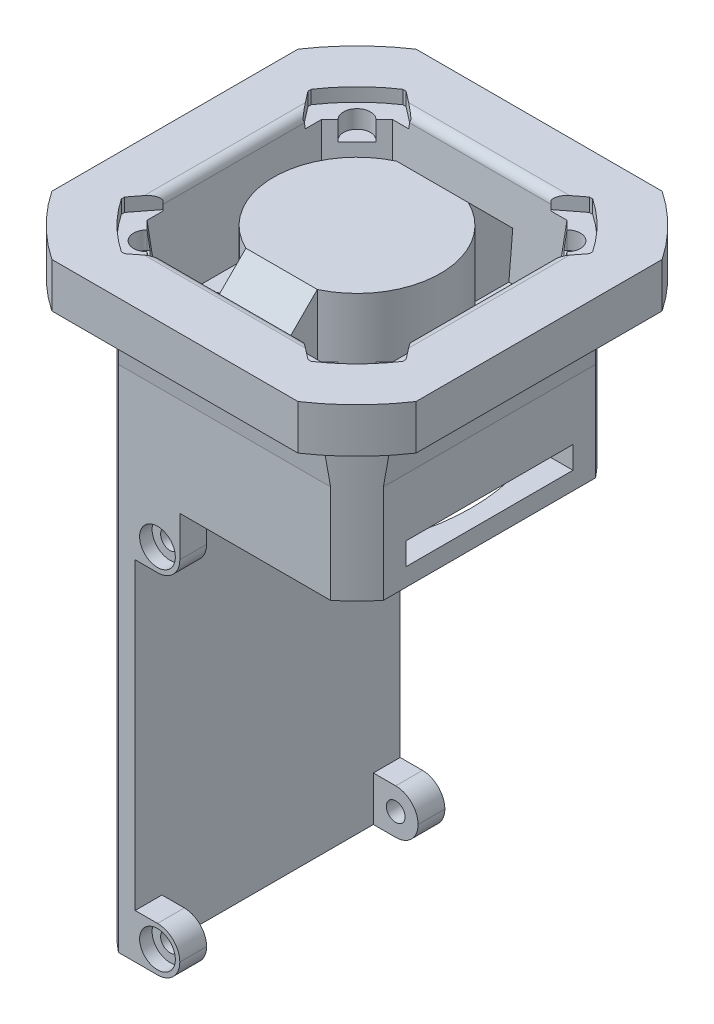
SolidWorks part; units mm, degrees
material "PVC 0.007 Plasticized"
ref_plane "Front Plane" through (0, 0, 0) normal (0, 0, 1) x (1, 0, 0)
ref_plane "Top Plane" through (0, 0, 0) normal (0, 1, 0) x (1, 0, 0)
ref_plane "Right Plane" through (0, 0, 0) normal (1, 0, 0) x (0, 0, -1)
sketch "Sketch1" plane through (0, 0, 0) normal (0, 1, 0) x (1, 0, 0)
  line L1 (0, 0) -> (30, 0)
  line L2 (0, 0) -> (0, 30)
  line L3 (0, 30) -> (30, 30)
  line L4 (30, 0) -> (30, 30)
  dimension "D1" = 30
  dimension "D2" = 30
extrude "Boss-Extrude1" add sketch "Sketch1" along normal blind 10
chamfer "Chamfer1" distance 2 angle 85 4 edges at (15, 0, 0) (30, 0, -15) (15, 0, -30) (0, 0, -15) first distance on face at (15, 0, -15)
shell "Shell1" thickness 2 removed face at (15, 10, -15) outward yes
fillet "Fillet1" radius 4 4 edges at (1.5626, 5, -28.4374) (1.5626, 5, -1.5626) (28.4374, 5, -1.5626) (28.4374, 5, -28.4374) profile chamfer
sketch "Sketch2" plane through (0, 0, 0) normal (0, 1, 0) x (-1, 0, 0)
  circle A1 centre (-15, -15) radius 19
  dimension "D1" = 38
extrude "Cut-Extrude2" cut sketch "Sketch2" along normal through all both and the other way through all flip side to cut
sketch "Sketch6" plane through (0, 0, 0) normal (0, 1, 0) x (1, 0, 0)
  line L0 (28, 24.0152) -> (28, 5.9848) construction
  line L1 (5.9848, 28) -> (24.0152, 28) construction
  circle A0 centre (15, 15) radius 8.1375
  point P4 (28, 15)
  point P7 (15, 28)
  dimension "D1" = 16.275
extrude "Cut-Extrude5" cut sketch "Sketch6" against normal blind 4
sketch "Sketch7" plane through (0, 0, 0) normal (0, 1, 0) x (1, 0, 0)
  line L0 (15, 28) -> (15, 2) construction
  line L1 (2, 5.9848) -> (2, 24.0152) construction
  line L6 (5.9848, 28) -> (24.0152, 28) construction
  line L7 (24.0152, 2) -> (5.9848, 2) construction
  line L8 (3.795, 4.1898) -> (3.795, 25.8102) construction
  line L9 (2, 5.9848) -> (5.9848, 2) construction
  line L10 (5.9848, 28) -> (2, 24.0152) construction
  line L11 (3.795, 15) -> (15, 15) construction
  circle A10 centre (3.795, 15) radius 1.59
  circle A11 centre (4.6394, 20.6315) radius 1.59
  circle A12 centre (8, 25.2285) radius 1.59
  circle A13 centre (4.6394, 9.3685) radius 1.59
  circle A14 centre (8, 4.7715) radius 1.59
  circle A15 centre (22, 4.7715) radius 1.59
  circle A16 centre (25.3606, 9.3685) radius 1.59
  circle A17 centre (26.205, 15) radius 1.59
  circle A18 centre (25.3606, 20.6315) radius 1.59
  circle A19 centre (22, 25.2285) radius 1.59
  arc A20 (3.795, 15) -> (15, 28) centre (15.6631, 16.0995) cw construction
  point P20 (15, 15)
  point P26 (15.6631, 16.0995)
  dimension "D1" = 7
  dimension "D2" = 1.795
  dimension "D3" = 3.18
  dimension "D4" = 3
  dimension "D5" = 5.75
extrude "Cut-Extrude7" cut sketch "Sketch7" against normal blind 0.71 contours A12 | A11 | A10 | A13 | A14 | A15 | A16 | A17 | A18 | A19
sketch "Sketch8" plane through (0, -0.71, 0) normal (0, 1, 0) x (1, 0, 0)
  circle A10 centre (8, 25.2285) radius 0.75
  circle A11 centre (4.6394, 20.6315) radius 0.75
  circle A12 centre (3.795, 15) radius 0.75
  circle A13 centre (4.6394, 9.3685) radius 0.75
  circle A14 centre (8, 4.7715) radius 0.75
  circle A15 centre (22, 25.2285) radius 0.75
  circle A16 centre (25.3606, 20.6315) radius 0.75
  circle A17 centre (26.205, 15) radius 0.75
  circle A18 centre (25.3606, 9.3685) radius 0.75
  circle A19 centre (22, 4.7715) radius 0.75
  dimension "D1" = 1.5
extrude "Cut-Extrude8" cut sketch "Sketch8" against normal through all
sketch "Sketch9" plane through (0, 10, 0) normal (0, 1, 0) x (1, 0, 0)
  line L0 (-0.8825, 25.4281) -> (1.1251, 22.8291)
  line L2 (1.1251, 22.8291) -> (7.1709, 28.8749)
  line L3 (1.1251, 24.8901) -> (5.1099, 28.8749) construction
  line L4 (1.1251, 24.8901) -> (1.1251, 5.1099) construction
  line L5 (24.8901, 28.8749) -> (5.1099, 28.8749) construction
  line L6 (7.1709, 28.8749) -> (4.5719, 30.8825)
  arc A2 (-0.8825, 25.4281) -> (4.5719, 30.8825) centre (15, 15) cw
  line M6 (1.1251, 5.1099) -> (1.1251, 24.8901)
  line M7 (1.1251, 24.8901) -> (5.1099, 28.8749)
  line M8 (5.1099, 28.8749) -> (24.8901, 28.8749)
  dimension "D1" = 8.55
  dimension "D2" = 0
extrude "Cut-Extrude10" cut sketch "Sketch9" against normal blind 1.5 contours L2 M6 M8 M7 | M6 M7 M8 region at (2.5018, 10, -27.4982) region at (3.668, 10, -26.332)
ref_plane "Plane1" through (15, 0, 0) normal (1, 0, 0) x (0, 0, -1)
ref_plane "Plane6" through (0, 0, -29.8327) normal (0, 0, 1) x (1, 0, 0)
mirror "Mirror1" about plane through (15, 0, 0) normal (1, 0, 0) of "Cut-Extrude10"
ref_plane "Plane2" through (0, 0, -15) normal (0, 0, 1) x (1, 0, 0)
mirror "Mirror2" about plane through (0, 0, -15) normal (0, 0, 1) of "Mirror1", "Cut-Extrude10"
sketch "Sketch10" plane through (0, 0, 0) normal (1, 0, 0) x (0, 0, -1)
  line L1 (0.5, -59) -> (29.5, -59)
  line L2 (0.5, -59) -> (0.5, -2)
  line L3 (0.5, -2) -> (29.5, -2)
  line L4 (29.5, -59) -> (29.5, -2)
  line L5 (26.874, -2) -> (3.126, -2) construction
  point P6 (15, -2)
  point P8 (15, -59)
  dimension "D1" = 29
  dimension "D2" = 57
extrude "Boss-Extrude2" add sketch "Sketch10" along normal blind 5
ref_plane "Plane3" through (0, 0, -15) normal (0, 0, 1) x (1, 0, 0)
sketch "Sketch15" plane through (0, 0, -29.8327) normal (0, 0, -1) x (-1, 0, 0)
  line L0 (-29.8327, -2) -> (-29.8327, -13)
  line L1 (-29.8327, -13) -> (-5, -13)
  line L2 (-5, -59) -> (-5, -2) construction
  line L3 (-5, -13) -> (-5, -10)
  line L4 (-5, -10) -> (-26.8327, -10)
  line L5 (-26.8327, -10) -> (-26.8327, -2)
  line L7 (-26.8327, -2) -> (-29.8327, -2)
  dimension "D1" = 11
  dimension "D2" = 3
  dimension "D3" = 3
extrude "Boss-Extrude4" add sketch "Sketch15" against normal up to vertex (29.6653 mm away) up to point (26.874, -2, -0.1673)
ref_plane "MIDPLANE" through (0, 0, -15) normal (0, 0, -1) x (-1, 0, 0)
sketch "Sketch16" plane through (0, -13, 0) normal (0, -1, 0) x (1, 0, 0)
  line L2 (2.205, -15) -> (27.795, -15) construction
  line L8 (26.8327, -3.1673) -> (8, -3.1673)
  line L9 (8, -3.1673) -> (8, -26.8327)
  line L10 (8, -26.8327) -> (26.8327, -26.8327)
  line L11 (26.8327, -26.8327) -> (26.8327, -3.1673)
  line L12 (24.144, -3.1673) -> (5.856, -3.1673)
  line L14 (5.856, -26.8327) -> (24.144, -26.8327)
  arc A1 (5.856, -3.1673) -> (5.856, -26.8327) centre (23.205, -15) ccw
  circle A2 centre (3.795, -15) radius 1.59 construction
  arc A3 (24.144, -3.1673) -> (24.144, -26.8327) centre (6.795, -15) cw
  circle A5 centre (26.205, -15) radius 1.59 construction
  dimension "D2" = 21
  dimension "D1" = 3
extrude "Cut-Extrude14" cut sketch "Sketch16" against normal up to surface (11 mm away) up to face at (10.6018, -2, -15)
sketch "Sketch17" plane through (29.8327, 0, 0) normal (1, 0, 0) x (0, 0, -1)
  line L12 (3.1673, -5) -> (3.1673, -10)
  line L13 (3.1673, -10) -> (26.8327, -10)
  line L14 (26.8327, -10) -> (26.8327, -5)
  line L15 (26.8327, -5) -> (3.1673, -5)
  line L16 (3.1673, -5) -> (3.1673, -10)
  line L17 (3.1673, -10) -> (26.8327, -10)
  line L18 (26.8327, -10) -> (26.8327, -5)
  line L19 (26.8327, -5) -> (3.1673, -5)
  dimension "D1" = 3
extrude "Cut-Extrude15" cut sketch "Sketch17" against normal blind 10
fillet "Fillet3" [suppressed] radius 3
sketch "Sketch18" [suppressed] plane through (0, 0, 0) normal (-1, 0, 0) x (0, 0, 1)
  line L4 (-0.5, -59) -> (-29.5, -59) construction
  line L12 (-6.5, -21) -> (-23.5, -21)
  line L13 (-23.5, -21) -> (-23.5, -53)
  line L14 (-23.5, -53) -> (-6.5, -53)
  line L15 (-6.5, -53) -> (-6.5, -21)
  dimension "D1" = 6
  dimension "D2" = 32
  dimension "D3" = 17
extrude "Cut-Extrude16" [suppressed] cut sketch "Sketch18" against normal through all
sketch "Sketch19" plane through (0, 8.5, 0) normal (0, 1, 0) x (1, 0, 0)
  line L2 (1.2563, 24.7589) -> (5.2411, 28.7437) construction
  line L3 (2.1881, 25.6906) -> (3.0811, 24.7975)
  line L4 (3.0811, 24.7975) -> (5.1997, 26.9161)
  line L5 (5.1997, 26.9161) -> (4.3094, 27.8119)
  arc A1 (2.1881, 25.6906) -> (4.3094, 27.8119) centre (3.2487, 26.7513) cw
  dimension "D3" = 1.5
  dimension "D2" = 3
extrude "Cut-Extrude18" cut sketch "Sketch19" against normal blind 2
mirror "Mirror4" about plane through (15, 0, 0) normal (1, 0, 0) of "Cut-Extrude18" second plane through (0, 0, -15) second plane normal (0, 0, 1)
fillet "Fillet6" radius 1 4 edges at (1.1251, 10, -15) (15, 10, -1.1251) (28.8749, 10, -15) (15, 10, -28.8749)
ref_plane "Plane4" through (0, 0, -15) normal (0, 0, -1) x (-1, 0, 0)
sketch "Sketch20" [suppressed] plane through (0, 0, -15) normal (0, 0, -1) x (-1, 0, 0)
  line L0 (0, -2) -> (0, -56) construction
  line L1 (0, -6) -> (0, -15.5)
  line L2 (0, -6) -> (9.5, -6)
  line L3 (0, -2) -> (-2.7048, -2) construction
  arc A0 (0, -15.5) -> (9.5, -6) centre (0, -6) ccw
  dimension "D1" = 4
  dimension "D2" = 9.5
extrude "Boss-Extrude5" [suppressed] add sketch "Sketch20" along normal mid plane 20
sketch "Sketch21" plane through (0, 0, 0) normal (0, 1, 0) x (1, 0, 0)
  circle A0 centre (15, 15) radius 9.3375
  circle A1 centre (15, 15) radius 8.1375
  circle A2 centre (15, 15) radius 8.1375 construction
  dimension "D1" = 18.675
extrude "Boss-Extrude6" add sketch "Sketch21" along normal blind 7
sketch "Sketch22" plane through (0, 7, 0) normal (0, 1, 0) x (1, 0, 0)
  circle A0 centre (15, 15) radius 9.3375
  circle A1 centre (15, 15) radius 9.3375 construction
  circle A2 centre (15, 15) radius 9.3375 construction
extrude "Boss-Extrude7" add sketch "Sketch22" along normal blind 1
ref_plane "Plane5" through (35.383, 0, 0) normal (1, 0, 0) x (0, 0, -1)
sketch "Sketch23" plane through (35.383, 0, 0) normal (1, 0, 0) x (0, 0, -1)
  line L1 (22, 10) -> (8, 10)
  line L2 (22, 10) -> (22, 5)
  line L3 (22, 5) -> (8, 5)
  line L4 (8, 10) -> (8, 5)
  line L5 (25.4281, 10) -> (4.5719, 10) construction
  point P7 (15, 10)
  point P8 (15, 10)
  dimension "D1" = 5
  dimension "D2" = 14
extrude "Boss-Extrude8" add sketch "Sketch23" against normal up to next
pattern_circular "CirPattern1" count 4 over 360 about axis through (15, 8, -15) along (0, 1, 0) skipping 2 of "Boss-Extrude8"
sketch "Sketch24" plane through (0, -2, 0) normal (0, 1, 0) x (1, 0, 0)
  line L2 (29.8327, 26.874) -> (29.8327, 29.8327)
  line L3 (29.8327, 26.874) -> (29.8327, 29.8327)
  line L4 (2.722, 29.5) -> (0, 29.5)
  line L5 (0, 29.5) -> (0, 0.5)
  line L6 (0, 0.5) -> (2.722, 0.5)
  line L7 (0.1673, 3.126) -> (0.1673, 26.874)
  line L8 (2.722, 29.5) -> (0, 29.5)
  line L9 (0, 29.5) -> (0, 0.5)
  line L10 (0, 0.5) -> (2.722, 0.5)
  line L11 (0.1673, 3.126) -> (0.1673, 26.874)
  line L14 (29.8327, 26.874) -> (29.8327, 29.8327)
  line L15 (29.8327, 26.874) -> (29.8327, 29.8327)
  line L18 (29.8327, 29.8327) -> (26.874, 29.8327)
  line L19 (29.8327, 29.8327) -> (26.874, 29.8327)
  line L20 (26.874, 0.1673) -> (29.8327, 0.1673)
  line L21 (29.8327, 0.1673) -> (29.8327, 3.126)
  line L23 (29.8327, 0.1673) -> (29.8327, 3.126)
  line L24 (29.8327, 29.8327) -> (26.874, 29.8327)
  line L25 (29.8327, 29.8327) -> (26.874, 29.8327)
  line L27 (26.874, 0.1673) -> (29.8327, 0.1673)
  arc A1 (29.8327, 26.874) -> (26.874, 29.8327) centre (15, 15) ccw
  arc A2 (2.722, 29.5) -> (0.1673, 26.874) centre (15, 15) ccw
  arc A3 (0.1673, 3.126) -> (2.722, 0.5) centre (15, 15) ccw
  arc A4 (2.722, 29.5) -> (0.1673, 26.874) centre (15, 15) ccw
  arc A5 (0.1673, 3.126) -> (2.722, 0.5) centre (15, 15) ccw
  arc A7 (29.8327, 26.874) -> (26.874, 29.8327) centre (15, 15) ccw
  arc A9 (29.8327, 26.874) -> (26.874, 29.8327) centre (15, 15) ccw
  arc A10 (26.874, 0.1673) -> (29.8327, 3.126) centre (15, 15) ccw
  arc A11 (26.874, 0.1673) -> (29.8327, 3.126) centre (15, 15) ccw
  arc A12 (29.8327, 26.874) -> (26.874, 29.8327) centre (15, 15) ccw
  arc M7 (0.1673, 26.874) -> (2.722, 29.5) centre (15, 15) cw
  line M8 (2.722, 29.5) -> (0, 29.5)
  line M9 (0, 29.5) -> (0, 0.5)
  line M10 (0, 0.5) -> (2.722, 0.5)
  arc M11 (2.722, 0.5) -> (0.1673, 3.126) centre (15, 15) cw
  line M12 (0.1673, 3.126) -> (0.1673, 26.874)
  dimension "D1" = 0
  dimension "D2" = 0
  dimension "D3" = 0
  dimension "D4" = 0
extrude "Cut-Extrude19" cut sketch "Sketch24" against normal up to surface (57 mm away) contours A11 L27 L23 | A12 L3 L25 | M12 M7 M8 M9 M10 M11 region at (28.8831, -2, -28.8831) region at (1.1724, -2, -28.4518) region at (28.8831, -2, -1.1169) up to face at (2.5, -59, -15)
sketch "Sketch25" plane through (0, -2, 0) normal (0, -1, 0) x (1, 0, 0)
  line L0 (5, -29.5) -> (2.722, -29.5) construction
  line L1 (3.126, -29.8327) -> (26.8327, -29.8327) construction
  line L2 (5, -29.5) -> (5, -29.8327) construction
  line L3 (5, -0.5) -> (2.722, -0.5) construction
  line L4 (5, -0.1673) -> (5, -0.5) construction
  line L5 (26.8327, -0.1673) -> (3.126, -0.1673) construction
  line L6 (5, -29.5) -> (2.722, -29.5)
  line L7 (3.126, -29.8327) -> (5, -29.8327)
  line L8 (5, -29.5) -> (5, -29.8327)
  line L9 (5, -0.5) -> (2.722, -0.5)
  line L10 (5, -0.1673) -> (5, -0.5)
  line L11 (26.8327, -0.1673) -> (3.126, -0.1673)
  line L12 (26.8327, -0.1673) -> (3.126, -0.1673) construction
  line L13 (5, -0.1673) -> (3.126, -0.1673)
  arc A0 (2.722, -29.5) -> (3.126, -29.8327) centre (15, -15) ccw construction
  arc A2 (2.722, -29.5) -> (3.126, -29.8327) centre (15, -15) ccw
  arc A4 (3.126, -0.1673) -> (2.722, -0.5) centre (15, -15) ccw construction
  arc A5 (3.126, -0.1673) -> (2.722, -0.5) centre (15, -15) ccw
  arc M3 (3.126, -0.1673) -> (2.722, -0.5) centre (15, -15) ccw
  line M4 (2.722, -0.5) -> (5, -0.5)
  line M32 (26.8327, -0.1673) -> (3.126, -0.1673)
extrude "Boss-Extrude9" add sketch "Sketch25" along normal up to surface (57 mm away) contours L10 M32 M3 M4 | L6 A2 L7 L8 region at (3.9578, -2, -0.3391) up to face at (2.6086, -59, -15)
sketch "Sketch51" plane through (0, -10, 0) normal (0, 1, 0) x (1, 0, 0)
  line L4 (26.8327, 26.8327) -> (26.8327, 29.8327)
  line L5 (26.8327, 3.1673) -> (29.8327, 3.1673)
  line L6 (29.8327, 3.1673) -> (29.8327, 26.8327)
  line L7 (29.8327, 26.8327) -> (26.8327, 26.8327)
  line L8 (26.8327, 26.8327) -> (26.8327, 29.8327)
  line L9 (26.8327, 3.1673) -> (29.8327, 3.1673)
  line L10 (29.8327, 3.1673) -> (29.8327, 26.8327)
  line L11 (29.8327, 26.8327) -> (26.8327, 26.8327)
  line L12 (24.144, 3.1673) -> (5.856, 3.1673)
  line L13 (5, 4.5321) -> (5, 0.1673)
  line L14 (5, 0.1673) -> (26.8327, 0.1673)
  line L15 (26.8327, 0.1673) -> (26.8327, 3.1673)
  line L16 (26.8327, 26.8327) -> (26.8327, 29.8327)
  line L17 (26.8327, 26.8327) -> (26.8327, 29.8327)
  line L18 (26.8327, 29.8327) -> (5, 29.8327)
  line L19 (26.8327, 29.8327) -> (5, 29.8327)
  line L20 (24.144, 3.1673) -> (5.856, 3.1673)
  line L21 (5, 4.5321) -> (5, 0.1673)
  line L22 (5, 0.1673) -> (26.8327, 0.1673)
  line L23 (26.8327, 0.1673) -> (26.8327, 3.1673)
  line L36 (5, 29.8327) -> (5, 25.4679)
  line L37 (5, 29.8327) -> (5, 25.4679)
  line L38 (5.856, 26.8327) -> (24.144, 26.8327)
  line L39 (5.856, 26.8327) -> (24.144, 26.8327)
  line L47 (26.8327, 0.1673) -> (26.8327, 3.1673)
  line L49 (26.8327, 3.1673) -> (29.8327, 3.1673)
  line L50 (26.8327, 3.1673) -> (29.8327, 3.1673)
  line L51 (29.8327, 3.1673) -> (29.8327, 26.8327)
  line L52 (29.8327, 3.1673) -> (29.8327, 26.8327)
  line L53 (29.8327, 26.8327) -> (26.8327, 26.8327)
  line L54 (29.8327, 26.8327) -> (26.8327, 26.8327)
  line L55 (24.144, 3.1673) -> (5.856, 3.1673)
  line L56 (24.144, 3.1673) -> (5.856, 3.1673)
  line L57 (5, 4.5321) -> (5, 0.1673)
  line L58 (5, 4.5321) -> (5, 0.1673)
  line L59 (5, 0.1673) -> (26.8327, 0.1673)
  line L60 (5, 0.1673) -> (26.8327, 0.1673)
  line L61 (26.8327, 0.1673) -> (26.8327, 3.1673)
  line L62 (26.8327, 0.1673) -> (26.8327, 3.1673)
  line L63 (26.8327, 29.8327) -> (5, 29.8327)
  line L64 (26.8327, 29.8327) -> (5, 29.8327)
  line L65 (5, 29.8327) -> (5, 25.4679)
  line L66 (5, 29.8327) -> (5, 25.4679)
  line L67 (5.856, 26.8327) -> (24.144, 26.8327)
  line L68 (5.856, 26.8327) -> (24.144, 26.8327)
  line L69 (24.144, 3.1673) -> (5.856, 3.1673)
  line L70 (24.144, 3.1673) -> (5.856, 3.1673)
  line L71 (5, 4.5321) -> (5, 0.1673)
  line L72 (5, 4.5321) -> (5, 0.1673)
  line L73 (5, 0.1673) -> (26.8327, 0.1673)
  line L74 (5, 0.1673) -> (26.8327, 0.1673)
  line L75 (26.8327, 3.1673) -> (29.8327, 3.1673)
  line L76 (26.8327, 3.1673) -> (29.8327, 3.1673)
  line L77 (29.8327, 3.1673) -> (29.8327, 26.8327)
  line L78 (29.8327, 3.1673) -> (29.8327, 26.8327)
  line L79 (29.8327, 26.8327) -> (26.8327, 26.8327)
  line L80 (29.8327, 26.8327) -> (26.8327, 26.8327)
  line L81 (26.8327, 26.8327) -> (26.8327, 29.8327)
  line L82 (26.8327, 26.8327) -> (26.8327, 29.8327)
  line L83 (26.8327, 29.8327) -> (5, 29.8327)
  line L84 (26.8327, 29.8327) -> (5, 29.8327)
  line L85 (5, 29.8327) -> (5, 25.4679)
  line L86 (5, 29.8327) -> (5, 25.4679)
  line L87 (5.856, 26.8327) -> (24.144, 26.8327)
  line L88 (5.856, 26.8327) -> (24.144, 26.8327)
  arc A1 (5.856, 26.8327) -> (5, 25.4679) centre (23.205, 15) ccw
  arc A3 (5.856, 26.8327) -> (5, 25.4679) centre (23.205, 15) ccw
  arc A5 (5, 4.5321) -> (5.856, 3.1673) centre (23.205, 15) ccw
  arc A6 (5, 4.5321) -> (5.856, 3.1673) centre (23.205, 15) ccw
  arc A9 (24.144, 3.1673) -> (24.144, 26.8327) centre (6.795, 15) ccw
  arc A10 (24.144, 3.1673) -> (24.144, 26.8327) centre (6.795, 15) ccw
  arc A11 (5, 4.5321) -> (5.856, 3.1673) centre (23.205, 15) ccw
  arc A12 (5, 4.5321) -> (5.856, 3.1673) centre (23.205, 15) ccw
  arc A13 (5.856, 26.8327) -> (5, 25.4679) centre (23.205, 15) ccw
  arc A14 (5.856, 26.8327) -> (5, 25.4679) centre (23.205, 15) ccw
  arc A15 (24.144, 3.1673) -> (24.144, 26.8327) centre (6.795, 15) ccw
  arc A16 (24.144, 3.1673) -> (24.144, 26.8327) centre (6.795, 15) ccw
  arc A17 (5, 4.5321) -> (5.856, 3.1673) centre (23.205, 15) ccw
  arc A18 (5, 4.5321) -> (5.856, 3.1673) centre (23.205, 15) ccw
  arc A19 (5.856, 26.8327) -> (5, 25.4679) centre (23.205, 15) ccw
  arc A20 (5.856, 26.8327) -> (5, 25.4679) centre (23.205, 15) ccw
  arc A21 (24.144, 3.1673) -> (24.144, 26.8327) centre (6.795, 15) ccw
  arc A22 (24.144, 3.1673) -> (24.144, 26.8327) centre (6.795, 15) ccw
  line M18 (26.8327, 29.8327) -> (5, 29.8327)
  line M19 (5, 29.8327) -> (5, 25.4679)
  line M20 (5.856, 26.8327) -> (24.144, 26.8327)
  dimension "D1" = 0
  dimension "D2" = 0
  dimension "D3" = 0
extrude "Boss-Extrude35" add sketch "Sketch51" along normal up to surface (8 mm away) contours L10 L11 L8 L9 | L22 L23 L20 L21 | M19 M20 M18 region at (28.3327, -10, -26.4458)
sketch "Sketch52" plane through (0, -13, 0) normal (0, -1, 0) x (1, 0, 0)
  line L0 (5.856, -3.1673) -> (5, -3.1673)
  line L1 (5, -0.1673) -> (5, -4.5321) construction
  line L2 (5, -3.1673) -> (5, -4.5321)
  line L3 (5.856, -26.8327) -> (5, -26.8327)
  line L4 (5, -25.4679) -> (5, -29.8327) construction
  line L5 (5, -26.8327) -> (5, -25.4679)
  arc A1 (5, -25.4679) -> (5.856, -26.8327) centre (23.205, -15) ccw construction
  arc A2 (5, -25.4679) -> (5.856, -26.8327) centre (23.205, -15) ccw
  arc A3 (5.856, -3.1673) -> (5, -4.5321) centre (23.205, -15) ccw construction
  arc A4 (5.856, -3.1673) -> (5, -4.5321) centre (23.205, -15) ccw
extrude "Cut-Extrude28" cut sketch "Sketch52" against normal up to surface (11 mm away)
sketch "Sketch26" plane through (0, 0, -29.8327) normal (0, 0, -1) x (-1, 0, 0)
  line L0 (-5, -59) -> (-5, -13) construction
  line L1 (-5, -59) -> (-10, -59)
  line L2 (-5, -59) -> (-5, -54)
  line L3 (-5, -54) -> (-10, -54)
  line L4 (-10, -59) -> (-10, -54)
  line L6 (-5, -13) -> (-5, -20)
  line L7 (-5, -20) -> (-10, -20)
  line L10 (-10, -20) -> (-10, -13)
  line L11 (-26.874, -13) -> (-5, -13) construction
  line L12 (-10, -13) -> (-5, -13)
  circle A0 centre (-7.5, -56.5) radius 2
  circle A1 centre (-7.5, -56.5) radius 1.05
  circle A2 centre (-7.5, -17.5) radius 2
  circle A3 centre (-7.5, -17.5) radius 1.05
  point P9 (-10, -56.5)
  point P10 (-7.5, -54)
  point P19 (-7.5, -20)
  line M17 (-26.874, -13) -> (-5, -13)
  line M18 (-5, -13) -> (-5, -59)
  dimension "D2" = 4
  dimension "D3" = 2.1
  dimension "D5" = 4
  dimension "D6" = 2.1
  dimension "D1" = 5
  dimension "D4" = 5
  dimension "D7" = 2.5
  dimension "D8" = 39
extrude "Boss-Extrude10" add sketch "Sketch26" against normal blind 3 contours L4 L1 L3 A0 M18 | L10 L7 A2 M18 M17 | A0 A1 | A2 A3 | A3 | A1 region at (7.5, -19.914, -29.8327) region at (7.5, -58.9293, -29.8327) region at (9.4434, -56.5, -29.8327) region at (9.4434, -17.5, -29.8327) region at (7.5, -17.5, -29.8327)
extrude "Cut-Extrude20" cut sketch "Sketch26<4>" against normal blind 1.4 contours A0 A1 | A2 A3 region at (9.4434, -56.5, -29.8327) region at (9.4434, -17.5, -29.8327)
sketch "Sketch26<4>" plane through (0, 0, -29.8327) normal (0, 0, -1) x (-1, 0, 0) same geometry as "Sketch26"
extrude "Cut-Extrude21" cut sketch "Sketch26<6>" against normal up to next contours A1 | A3 region at (7.5, -56.5, -29.8327) region at (7.5, -17.5, -29.8327)
sketch "Sketch26<6>" plane through (0, 0, -29.8327) normal (0, 0, -1) x (-1, 0, 0) same geometry as "Sketch26"
mirror "Mirror5" about plane through (0, 0, -15) normal (0, 0, -1) of "Boss-Extrude9", "Boss-Extrude10", "Cut-Extrude20", "Cut-Extrude21"
fillet "Fillet7" radius 2.5 6 edges at (10, -20, -28.3327) (10, -54, -28.3327) (10, -59, -28.3327) (10, -20, -1.6673) (10, -54, -1.6673) (10, -59, -1.6673)
sketch "Sketch28" plane through (0, 0, 5.383) normal (0, 0, 1) x (1, 0, 0)
  line L1 (35.383, 10) -> (35.383, 5) construction
  line L2 (35.383, 10) -> (35.383, 5)
  line L4 (22, 5) -> (22, 10)
  line L5 (22, 10) -> (8, 10)
  line L6 (8, 10) -> (8, 5)
  line L7 (8, 5) -> (22, 5)
  line L9 (35.383, 10) -> (8, 10)
  line L10 (8, 10) -> (8, 5)
  line L11 (8, 5) -> (35.383, 5)
  line M5 (22, 5) -> (22, 10)
  dimension "D1" = 0
extrude "Boss-Extrude19" add sketch "Sketch28" against normal up to surface (4.5005 mm away) contours L11 L2 L9 M5 region at (28.6915, 7.5, 5.383) up to face at (15, 6.6909, 0.593)
sketch "Sketch30" plane through (35.383, 0, 0) normal (1, 0, 0) x (0, 0, -1)
  line L0 (-0.4451, 5) -> (8, 5)
  line L1 (8, 5) -> (8, 10)
  line L2 (8, 10) -> (-0.8825, 10)
  line L3 (-0.8825, 10) -> (-0.4451, 5)
extrude "Boss-Extrude21" add sketch "Sketch30" against normal up to surface (4.5005 mm away) up to face at (30.593, 6.6909, -15)
sketch "Sketch31" plane through (0, 10, 0) normal (0, 1, 0) x (1, 0, 0)
  line L14 (25.6253, -0.7513) -> (25.2582, -0.7513) construction
  line L15 (24.0154, 0.2088) -> (25.4281, -0.8825) construction
  line L16 (25.4281, -0.8825) -> (30.8825, -0.8825) construction
  line L18 (30.8825, -0.8825) -> (30.8825, 4.5719) construction
  line L19 (25.6253, -0.7513) -> (25.2582, -0.7513)
  line L20 (25.2582, -0.7513) -> (25.4281, -0.8825)
  line L21 (25.4281, -0.8825) -> (30.8825, -0.8825)
  line L29 (30.8825, 4.5719) -> (29.7912, 5.9846) construction
  line L30 (30.8825, -0.8825) -> (30.8825, 4.5719)
  line L31 (30.7513, 4.7418) -> (30.7513, 4.3747) construction
  line L32 (30.8825, 4.5719) -> (30.7513, 4.7418)
  line L33 (30.7513, 4.7418) -> (30.7513, 4.3747)
  arc A4 (25.6253, -0.7513) -> (30.7513, 4.3747) centre (15, 15) ccw construction
  arc A7 (25.6253, -0.7513) -> (30.7513, 4.3747) centre (15, 15) ccw
extrude "Boss-Extrude22" add sketch "Sketch31" against normal up to surface (5 mm away) up to face at (25.5209, 5, -4.4791)
mirror "Mirror6" about plane through (0, 0, -15) normal (0, 0, 1) of "Boss-Extrude21"
sketch "Sketch33" plane through (22, 0, 0) normal (1, 0, 0) x (0, 0, -1)
  line L4 (30.8825, 10) -> (30.4451, 5)
  line L5 (30.4451, 5) -> (35.383, 5)
  line L6 (35.383, 5) -> (35.383, 10)
  line L7 (35.383, 10) -> (30.8825, 10)
  line L8 (30.8825, 10) -> (30.4451, 5)
  line L9 (30.4451, 5) -> (35.383, 5)
  line L10 (35.383, 5) -> (35.383, 10)
  line L11 (35.383, 10) -> (30.8825, 10)
  dimension "D1" = 0
extrude "Boss-Extrude23" add sketch "Sketch33" along normal up to surface (13.383 mm away) up to face at (35.383, 7.5, -12.6404)
sketch "Sketch34" plane through (0, 10, 0) normal (0, 1, 0) x (1, 0, 0)
  line L0 (30.7513, 25.6253) -> (30.7513, 25.2582) construction
  line L1 (30.8825, 25.4281) -> (29.7912, 24.0154) construction
  line L2 (30.8825, 30.8825) -> (30.8825, 25.4281) construction
  line L3 (30.8825, 30.8825) -> (25.4281, 30.8825) construction
  line L4 (24.0154, 29.7912) -> (25.4281, 30.8825) construction
  line L5 (25.2582, 30.7513) -> (25.6253, 30.7513) construction
  line L6 (30.7513, 25.6253) -> (30.7513, 25.2582)
  line L7 (30.8825, 25.4281) -> (30.7513, 25.2582)
  line L8 (30.8825, 30.8825) -> (30.8825, 25.4281)
  line L9 (30.8825, 30.8825) -> (25.4281, 30.8825)
  line L10 (25.2582, 30.7513) -> (25.4281, 30.8825)
  line L11 (25.2582, 30.7513) -> (25.6253, 30.7513)
  arc A0 (30.7513, 25.6253) -> (25.6253, 30.7513) centre (15, 15) ccw construction
  arc A1 (30.7513, 25.6253) -> (25.6253, 30.7513) centre (15, 15) ccw
extrude "Boss-Extrude25" add sketch "Sketch34" against normal up to surface (5 mm away) up to face at (22.4011, 5, -16.3878)
sketch "Sketch35" plane through (0, 10, 0) normal (0, 1, 0) x (1, 0, 0)
  line L2 (35.383, 35.383) -> (35.383, -5.383) construction
  line L3 (-0.8825, 15) -> (35.383, 15) construction
  line L4 (-0.8825, 25.4281) -> (-0.8825, 4.5719) construction
  line L10 (35.383, -5.383) -> (8, -5.383) construction
  line L11 (35.383, -5.383) -> (28.7729, -5.383)
  line L12 (35.383, 35.383) -> (35.383, 15)
  line L13 (35.383, 1.2271) -> (35.383, -5.383)
  line L14 (35.383, 35.383) -> (28.7729, 35.383)
  line L15 (35.383, 28.7729) -> (35.383, 35.383)
  arc A4 (28.7729, 35.383) -> (35.383, 28.7729) centre (15, 15) cw
  arc A5 (28.757, -5.3938) -> (35.3938, 1.243) centre (15, 15) ccw
  arc A6 (28.7729, -5.383) -> (35.383, 1.2271) centre (15, 15) ccw
  arc A8 (25.6253, -0.7513) -> (30.7513, 4.3747) centre (15, 15) ccw construction
  line M20 (8, -5.383) -> (35.383, -5.383)
  line M21 (35.383, -5.383) -> (35.383, 35.383)
  line M22 (35.383, 35.383) -> (8, 35.383)
  dimension "D1" = 5.6
extrude "Cut-Extrude22" cut sketch "Sketch35" against normal up to surface (5 mm away) contours A6 M20 M21 | A4 L12 M22 region at (33.3228, 10, -33.3228) region at (33.3228, 10, 3.3228) up to face at (21.6147, 5, -15)
sketch "Sketch39" plane through (8, 0, 0) normal (-1, 0, 0) x (0, 0, 1)
  line L4 (-30.4451, 5) -> (-30.8825, 10)
  line L5 (-30.8825, 10) -> (-35.383, 10)
  line L6 (-35.383, 10) -> (-35.383, 5)
  line L7 (-35.383, 5) -> (-30.4451, 5)
  line L8 (-30.4451, 5) -> (-30.8825, 10)
  line L9 (-30.8825, 10) -> (-35.383, 10)
  line L10 (-35.383, 10) -> (-35.383, 5)
  line L11 (-35.383, 5) -> (-30.4451, 5)
  dimension "D1" = 0
mirror "Mirror10" about plane through (15, 0, 0) normal (1, 0, 0) of "Boss-Extrude8", "Boss-Extrude19", "Boss-Extrude23"
sketch "Sketch41" [suppressed] plane through (-5.383, 0, 0) normal (-1, 0, 0) x (0, 0, 1)
  line L0 (-30.4451, 5) -> (-22, 5)
  line L1 (-22, 5) -> (-22, 10)
  line L2 (-22, 10) -> (-30.8825, 10)
  line L3 (-30.8825, 10) -> (-30.4451, 5)
sketch "Sketch44" plane through (0, 0, -22) normal (0, 0, -1) x (-1, 0, 0)
  line L4 (5.383, 10) -> (0.8825, 10)
  line L5 (0.8825, 10) -> (0.4451, 5)
  line L6 (0.4451, 5) -> (5.383, 5)
  line L7 (5.383, 5) -> (5.383, 10)
  line L8 (5.383, 10) -> (0.8825, 10)
  line L9 (0.8825, 10) -> (0.4451, 5)
  line L10 (0.4451, 5) -> (5.383, 5)
  line L11 (5.383, 5) -> (5.383, 10)
  dimension "D1" = 0
extrude "Boss-Extrude32" add sketch "Sketch44" along normal up to surface and the other way up to surface up to face at (1.1426, 7.8363, -30.6932) other way up to face at (1.1426, 7.8363, 0.6932)
sketch "Sketch45" plane through (0, 10, 0) normal (0, 1, 0) x (1, 0, 0)
  line L3 (-0.7513, 25.2582) -> (-0.7513, 25.6253) construction
  line L4 (-0.8825, 25.4281) -> (0.2088, 24.0154) construction
  line L5 (-0.8825, 30.8825) -> (-0.8825, 25.4281) construction
  line L6 (-0.8825, 30.8825) -> (4.5719, 30.8825) construction
  line L7 (5.9846, 29.7912) -> (4.5719, 30.8825) construction
  line L8 (4.3747, 30.7513) -> (4.7418, 30.7513) construction
  line L10 (-0.7513, 25.2582) -> (-0.7513, 25.6253)
  line L11 (-0.8825, 25.4281) -> (-0.7513, 25.2582)
  line L12 (-0.8825, 30.8825) -> (-0.8825, 25.4281)
  line L13 (-0.8825, 30.8825) -> (4.5719, 30.8825)
  line L14 (4.7418, 30.7513) -> (4.5719, 30.8825)
  line L15 (4.3747, 30.7513) -> (4.7418, 30.7513)
  arc A0 (4.3747, 30.7513) -> (-0.7513, 25.6253) centre (15, 15) ccw construction
  arc A1 (4.3747, 30.7513) -> (-0.7513, 25.6253) centre (15, 15) ccw
extrude "Boss-Extrude33" add sketch "Sketch45" against normal up to surface (5 mm away) up to face at (19.6966, 5, -15)
mirror "Mirror11" about plane through (0, 0, -15) normal (0, 0, 1) of "Boss-Extrude33"
sketch "Sketch46" plane through (0, 10, 0) normal (0, 1, 0) x (1, 0, 0)
  line L0 (-5.383, 35.383) -> (28.7729, 35.383) construction
  line L1 (-5.383, 35.383) -> (-5.383, -5.383) construction
  line L2 (-5.383, 35.383) -> (1.2271, 35.383)
  line L3 (-5.383, 35.383) -> (-5.383, 28.7729)
  arc A9 (1.243, 35.3938) -> (-5.3938, 28.757) centre (15, 15) ccw
  arc A10 (1.2271, 35.383) -> (-5.383, 28.7729) centre (15, 15) ccw
  dimension "D1" = 5.6
extrude "Cut-Extrude24" cut sketch "Sketch46" against normal up to surface (5 mm away) up to face at (15, 5, -15)
mirror "Mirror12" about plane through (0, 0, -15) normal (0, 0, 1) of "Cut-Extrude24"
sketch "Sketch47" plane through (0, 0, 0) normal (0, 1, 0) x (1, 0, 0)
  line L0 (15, 28) -> (15, 2) construction
  line L1 (5.9848, 28) -> (24.0152, 28) construction
  line L2 (24.0152, 2) -> (5.9848, 2) construction
  line L3 (2, 15) -> (28, 15) construction
  line L4 (2, 5.9848) -> (2, 24.0152) construction
  line L5 (28, 24.0152) -> (28, 5.9848) construction
  line L6 (11, 23.69) -> (11, 28.795)
  line L16 (22.909, 28.795) -> (7.091, 28.795) construction
  line L17 (19, 28.795) -> (11, 28.795)
  line L18 (7.091, 1.205) -> (22.909, 1.205) construction
  line L19 (11, 1.205) -> (19, 1.205)
  line L20 (11, 26.2425) -> (11, 23.69) construction
  line L22 (11, 23.69) -> (11, 23.4374)
  line L23 (19, 23.69) -> (19, 28.795)
  line L24 (19, 23.69) -> (19, 23.4374)
  line L25 (19, 6.31) -> (19, 1.205)
  line L26 (19, 6.31) -> (19, 6.5626)
  line L27 (11, 6.31) -> (11, 6.5626)
  line L28 (11, 6.31) -> (11, 1.205)
  line L29 (11, 23.4374) -> (19, 23.4374) construction
  circle A6 centre (15, 15) radius 9.3375 construction
  circle A13 centre (15, 15) radius 9.3375
  arc A14 (11, 23.4374) -> (11, 6.5626) centre (15, 15) ccw
  arc A15 (19, 6.5626) -> (19, 23.4374) centre (15, 15) ccw
  line M15 (24.0152, 28) -> (5.9848, 28)
  line M19 (5.9848, 2) -> (24.0152, 2)
  circle M26 centre (15, 15) radius 9.3375
  dimension "D2" = 0
  dimension "D1" = 8
extrude "Boss-Extrude34" add sketch "Sketch47" along normal up to surface (10 mm away) contours L24 L23 L6 L22 M15 M26 | L27 L28 L25 L26 M19 M26 | L28 L19 L25 M19 | L23 L17 L6 M15 | M26 region at (15, 0, -26.0128) region at (15, 0, -28.3975) region at (15, 0, -15) region at (15, 0, -3.9872) region at (15, 0, -1.6025) up to face at (15, 10, -15)
fillet "Fillet8" [suppressed] radius 4
fillet "Fillet9" [suppressed] radius 3
sketch "Sketch48" plane through (19, 0, 0) normal (1, 0, 0) x (0, 0, -1)
  line L0 (6.5626, 10) -> (1.5626, 4.9999)
  line L2 (2, 0) -> (1.205, 9.0872) construction
  line L3 (6.5626, 10) -> (1.1251, 10)
  line L4 (1.5626, 4.9999) -> (1.1251, 10)
  line L5 (23.4374, 10) -> (6.5626, 10) construction
  line L6 (23.4374, 10) -> (6.5626, 10) construction
  line L7 (1.205, 10) -> (6.5626, 10) construction
  line L8 (1.205, 9.0872) -> (2, 0) construction
  dimension "D1" = 45
extrude "Cut-Extrude25" cut sketch "Sketch48" against normal up to next
mirror "Mirror13" about plane through (0, 0, -15) normal (0, 0, 1) of "Cut-Extrude25"
sketch "Sketch50" plane through (0, 0, 0) normal (0, -1, 0) x (1, 0, 0)
  circle A1 centre (15, -15) radius 8.1375
  circle A3 centre (15, -15) radius 8.1375
  dimension "D1" = 0
extrude "Cut-Extrude26" cut sketch "Sketch50" against normal blind 8
sketch "Sketch53" plane through (0, -2, 0) normal (0, -1, 0) x (1, 0, 0)
  circle A0 centre (15, -15) radius 8.1375 construction
  circle A1 centre (15, -15) radius 8.1375
  circle A2 centre (15, -15) radius 9.34
  dimension "D1" = 18.68
extrude "Boss-Extrude37" add sketch "Sketch53" along normal blind 6.5
sketch "Sketch55" plane through (29.8327, 0, 0) normal (1, 0, 0) x (0, 0, -1)
  line L0 (26.874, -2) -> (3.126, -2) construction
  line L1 (5.66, -8.5) -> (24.34, -8.5)
  line L2 (5.66, -8.5) -> (5.66, -11)
  line L3 (5.66, -11) -> (24.34, -11)
  line L4 (24.34, -8.5) -> (24.34, -11)
  line L5 (5.66, -8.5) -> (24.34, -8.5) construction
  line L7 (3.126, -13) -> (26.874, -13) construction
  line L8 (5.66, -8.5) -> (24.34, -8.5)
  point P6 (15, -2)
  point P7 (15, -8.5)
  dimension "D1" = 2
extrude "Cut-Extrude30" cut sketch "Sketch55" against normal through all contours L1 L2 L3 L4
